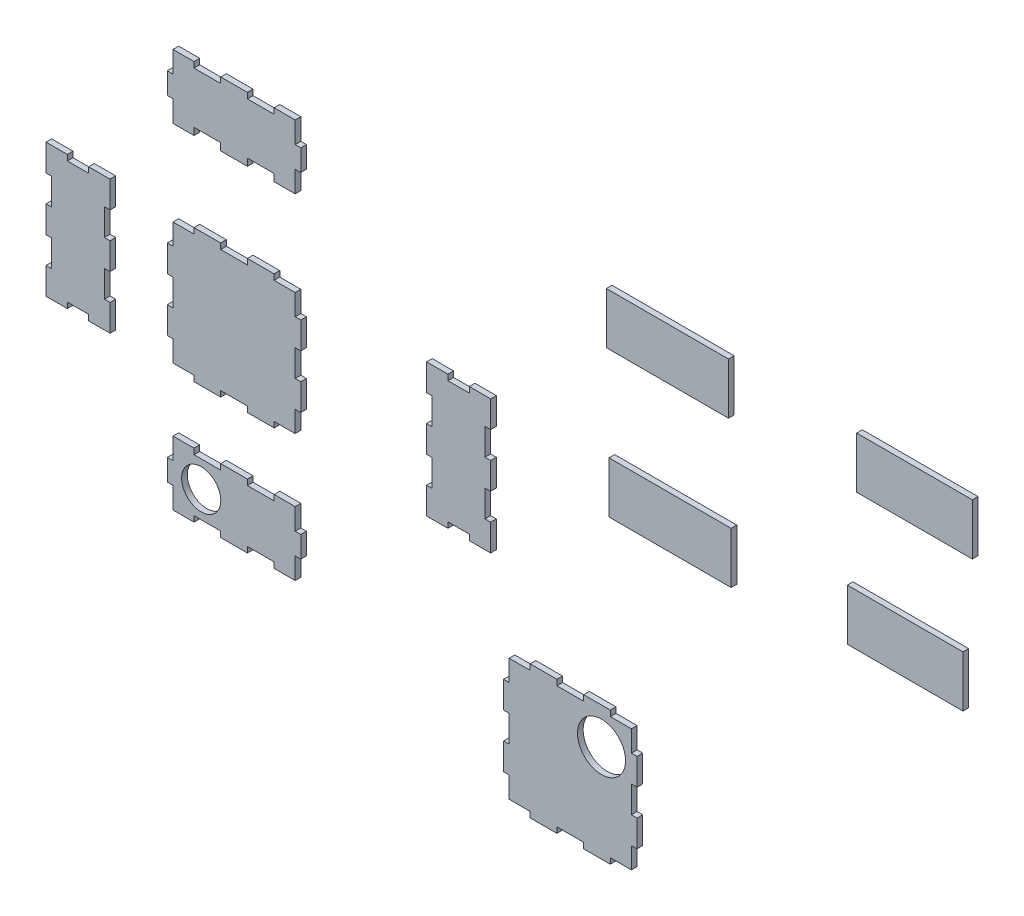
SolidWorks part; units mm, degrees
ref_plane "Front Plane" through (0, 0, 0) normal (0, 0, 1) x (1, 0, 0)
ref_plane "Top Plane" through (0, 0, 0) normal (0, 1, 0) x (1, 0, 0)
ref_plane "Right Plane" through (0, 0, 0) normal (1, 0, 0) x (0, 0, -1)
sketch "Sketch1" plane through (0, 0, 0) normal (0, 0, 1) x (1, 0, 0)
  line L0 (58.1679, -14.5353) -> (133.1679, -14.5353)
  line L1 (-130.7492, 103.2806) -> (-55.7492, 103.2806)
  line L2 (-130.7492, 103.2806) -> (-130.7492, 28.2806)
  line L3 (-130.7492, 28.2806) -> (-55.7492, 28.2806)
  line L4 (-55.7492, 103.2806) -> (-55.7492, 28.2806)
  line L5 (-130.7492, 184.0678) -> (-55.7492, 184.0678)
  line L6 (-130.7492, 184.0678) -> (-130.7492, 148.0678)
  line L7 (-130.7492, 148.0678) -> (-55.7492, 148.0678)
  line L8 (-55.7492, 184.0678) -> (-55.7492, 148.0678)
  line L9 (-162.8947, 103.2806) -> (-198.8947, 103.2806)
  line L10 (-162.8947, 103.2806) -> (-162.8947, 28.2806)
  line L11 (-162.8947, 28.2806) -> (-198.8947, 28.2806)
  line L12 (-198.8947, 103.2806) -> (-198.8947, 28.2806)
  line L13 (-130.7492, -4.048) -> (-55.7492, -4.048)
  line L14 (-130.7492, -4.048) -> (-130.7492, -40.048)
  line L15 (-130.7492, -40.048) -> (-55.7492, -40.048)
  line L16 (-55.7492, -4.048) -> (-55.7492, -40.048)
  line L17 (14.9083, 103.2806) -> (50.9083, 103.2806)
  line L18 (14.9083, 103.2806) -> (14.9083, 28.2806)
  line L19 (14.9083, 28.2806) -> (50.9083, 28.2806)
  line L20 (50.9083, 103.2806) -> (50.9083, 28.2806)
  line L21 (58.1679, -14.5353) -> (58.1679, -89.5353)
  line L22 (58.1679, -89.5353) -> (133.1679, -89.5353)
  line L23 (133.1679, -14.5353) -> (133.1679, -89.5353)
  line L24 (117.4177, 107.8353) -> (186.0177, 107.8353)
  line L25 (115.9298, 189.4652) -> (184.5298, 189.4652)
  line L26 (115.9298, 189.4652) -> (115.9298, 160.6652)
  line L27 (115.9298, 160.6652) -> (184.5298, 160.6652)
  line L28 (184.5298, 189.4652) -> (184.5298, 160.6652)
  line L29 (117.4177, 107.8353) -> (117.4177, 79.0353)
  line L30 (117.4177, 79.0353) -> (186.0177, 79.0353)
  line L31 (186.0177, 107.8353) -> (186.0177, 79.0353)
  line L32 (251.2924, 112.8623) -> (316.2924, 112.8623)
  line L33 (256.5253, 189.4652) -> (321.5253, 189.4652)
  line L34 (256.5253, 189.4652) -> (256.5253, 160.6652)
  line L35 (256.5253, 160.6652) -> (321.5253, 160.6652)
  line L36 (321.5253, 189.4652) -> (321.5253, 160.6652)
  line L37 (251.2924, 112.8623) -> (251.2924, 84.0623)
  line L38 (251.2924, 84.0623) -> (316.2924, 84.0623)
  line L39 (316.2924, 112.8623) -> (316.2924, 84.0623)
  dimension "D1" = 75
  dimension "D2" = 75
  dimension "D3" = 36
  dimension "D4" = 36
  dimension "D5" = 36
  dimension "D6" = 36
  dimension "D7" = 75
  dimension "D8" = 75
  dimension "D9" = 75
  dimension "D10" = 75
  dimension "D11" = 75
  dimension "D12" = 68.6
  dimension "D13" = 28.8
  dimension "D14" = 68.6
  dimension "D15" = 28.8
  dimension "D16" = 65
  dimension "D17" = 28.8
  dimension "D18" = 65
  dimension "D19" = 28.8
extrude "Boss-Extrude1" add sketch "Sketch1" along normal blind 3.18
sketch "Sketch2" plane through (0, 0, 3.18) normal (0, 0, 1) x (1, 0, 0)
  line L0 (-130.7492, 103.2806) -> (-130.7492, 28.2806) construction
  line L1 (-130.7492, 103.2806) -> (-127.5692, 103.2806)
  line L2 (-130.7492, 103.2806) -> (-130.7492, 88.2806)
  line L3 (-130.7492, 88.2806) -> (-127.5692, 88.2806)
  line L4 (-127.5692, 103.2806) -> (-127.5692, 88.2806)
  line L5 (-127.5692, 88.2806) -> (-130.7492, 88.2806)
  line L6 (-127.5692, 88.2806) -> (-127.5692, 73.2806)
  line L7 (-127.5692, 73.2806) -> (-130.7492, 73.2806)
  line L8 (-130.7492, 88.2806) -> (-130.7492, 73.2806)
  line L9 (-58.9292, 103.2806) -> (-55.7492, 103.2806)
  line L10 (-127.5692, 73.2806) -> (-130.7492, 73.2806)
  line L11 (-127.5692, 73.2806) -> (-127.5692, 58.2806)
  line L12 (-127.5692, 58.2806) -> (-130.7492, 58.2806)
  line L13 (-130.7492, 73.2806) -> (-130.7492, 58.2806)
  line L14 (-127.5692, 58.2806) -> (-130.7492, 58.2806)
  line L15 (-127.5692, 58.2806) -> (-127.5692, 43.2806)
  line L16 (-127.5692, 43.2806) -> (-130.7492, 43.2806)
  line L17 (-130.7492, 58.2806) -> (-130.7492, 43.2806)
  line L18 (-127.5692, 43.2806) -> (-130.7492, 43.2806)
  line L19 (58.1259, -14.5353) -> (61.3059, -14.5353)
  line L20 (-130.7492, 28.2806) -> (-115.7492, 28.2806)
  line L21 (-130.7492, 28.2806) -> (-130.7492, 31.4606)
  line L22 (-58.9292, 103.2806) -> (-58.9292, 88.2806)
  line L23 (-58.9292, 88.2806) -> (-55.7492, 88.2806)
  line L24 (-55.7492, 103.2806) -> (-55.7492, 88.2806)
  line L25 (-55.7492, 88.2806) -> (-58.9292, 88.2806)
  line L26 (-55.7492, 88.2806) -> (-55.7492, 73.2806)
  line L27 (-55.7492, 73.2806) -> (-58.9292, 73.2806)
  line L28 (-58.9292, 88.2806) -> (-58.9292, 73.2806)
  line L29 (-55.7492, 73.2806) -> (-58.9292, 73.2806)
  line L30 (-55.7492, 73.2806) -> (-55.7492, 58.2806)
  line L31 (-55.7492, 58.2806) -> (-58.9292, 58.2806)
  line L32 (-58.9292, 73.2806) -> (-58.9292, 58.2806)
  line L33 (-55.7492, 58.2806) -> (-58.9292, 58.2806)
  line L34 (-55.7492, 58.2806) -> (-55.7492, 43.2806)
  line L35 (-55.7492, 43.2806) -> (-58.9292, 43.2806)
  line L36 (-58.9292, 58.2806) -> (-58.9292, 43.2806)
  line L37 (-55.7492, 43.2806) -> (-58.9292, 43.2806)
  line L38 (-55.7492, 43.2806) -> (-55.7492, 28.2806)
  line L39 (-55.7492, 28.2806) -> (-58.9292, 28.2806)
  line L40 (-58.9292, 43.2806) -> (-58.9292, 28.2806)
  line L41 (-55.7492, 103.2806) -> (-130.7492, 103.2806) construction
  line L42 (-55.7492, 28.2806) -> (-55.7492, 103.2806) construction
  line L43 (-130.7492, 28.2806) -> (-55.7492, 28.2806) construction
  line L44 (-130.7492, 31.4606) -> (-115.7492, 31.4606)
  line L45 (-115.7492, 28.2806) -> (-115.7492, 31.4606)
  line L46 (-115.7492, 31.4606) -> (-100.7492, 31.4606)
  line L47 (-115.7492, 31.4606) -> (-115.7492, 28.2806)
  line L48 (-115.7492, 28.2806) -> (-100.7492, 28.2806)
  line L49 (-100.7492, 31.4606) -> (-100.7492, 28.2806)
  line L50 (-100.7492, 28.2806) -> (-85.7492, 28.2806)
  line L51 (-100.7492, 28.2806) -> (-100.7492, 31.4606)
  line L52 (-100.7492, 31.4606) -> (-85.7492, 31.4606)
  line L53 (-85.7492, 28.2806) -> (-85.7492, 31.4606)
  line L54 (-85.7492, 31.4606) -> (-70.7492, 31.4606)
  line L55 (-85.7492, 31.4606) -> (-85.7492, 28.2806)
  line L56 (-85.7492, 28.2806) -> (-70.7492, 28.2806)
  line L57 (-70.7492, 31.4606) -> (-70.7492, 28.2806)
  line L58 (-70.7492, 28.2806) -> (-55.7492, 28.2806)
  line L59 (-70.7492, 28.2806) -> (-70.7492, 31.4606)
  line L60 (-70.7492, 31.4606) -> (-55.7492, 31.4606)
  line L61 (-55.7492, 28.2806) -> (-55.7492, 31.4606)
  line L62 (-127.5692, 43.2806) -> (-130.7492, 43.2806)
  line L63 (-127.5692, 43.2806) -> (-127.5692, 28.2806)
  line L64 (-127.5692, 28.2806) -> (-130.7492, 28.2806)
  line L65 (-130.7492, 43.2806) -> (-130.7492, 28.2806)
  line L66 (-130.7492, 103.2806) -> (-115.7492, 103.2806)
  line L67 (-130.7492, 103.2806) -> (-130.7492, 100.1006)
  line L68 (-130.7492, 100.1006) -> (-115.7492, 100.1006)
  line L69 (-115.7492, 103.2806) -> (-115.7492, 100.1006)
  line L70 (-115.7492, 100.1006) -> (-100.7492, 100.1006)
  line L71 (-115.7492, 100.1006) -> (-115.7492, 103.2806)
  line L72 (-115.7492, 103.2806) -> (-100.7492, 103.2806)
  line L73 (-100.7492, 100.1006) -> (-100.7492, 103.2806)
  line L74 (-100.7492, 100.1006) -> (-85.7492, 100.1006)
  line L75 (-100.7492, 100.1006) -> (-100.7492, 103.2806)
  line L76 (-100.7492, 103.2806) -> (-85.7492, 103.2806)
  line L77 (-85.7492, 100.1006) -> (-85.7492, 103.2806)
  line L78 (-85.7492, 100.1006) -> (-70.7492, 100.1006)
  line L79 (-85.7492, 100.1006) -> (-85.7492, 103.2806)
  line L80 (-85.7492, 103.2806) -> (-70.7492, 103.2806)
  line L81 (-70.7492, 100.1006) -> (-70.7492, 103.2806)
  line L82 (-70.7492, 100.1006) -> (-55.7492, 100.1006)
  line L83 (-70.7492, 100.1006) -> (-70.7492, 103.2806)
  line L84 (-70.7492, 103.2806) -> (-55.7492, 103.2806)
  line L85 (-55.7492, 100.1006) -> (-55.7492, 103.2806)
  line L86 (58.1259, -14.5353) -> (58.1259, -29.5353)
  line L87 (58.1259, -29.5353) -> (61.3059, -29.5353)
  line L88 (61.3059, -14.5353) -> (61.3059, -29.5353)
  line L89 (61.3059, -29.5353) -> (58.1259, -29.5353)
  line L90 (61.3059, -29.5353) -> (61.3059, -44.5353)
  line L91 (61.3059, -44.5353) -> (58.1259, -44.5353)
  line L92 (58.1259, -29.5353) -> (58.1259, -44.5353)
  line L93 (129.9879, -14.5353) -> (133.1679, -14.5353)
  line L94 (61.3059, -44.5353) -> (58.1259, -44.5353)
  line L95 (61.3059, -44.5353) -> (61.3059, -59.5353)
  line L96 (61.3059, -59.5353) -> (58.1259, -59.5353)
  line L97 (58.1259, -44.5353) -> (58.1259, -59.5353)
  line L98 (61.3059, -59.5353) -> (58.1259, -59.5353)
  line L99 (61.3059, -59.5353) -> (61.3059, -74.5353)
  line L100 (61.3059, -74.5353) -> (58.1259, -74.5353)
  line L101 (58.1259, -59.5353) -> (58.1259, -74.5353)
  line L102 (61.3059, -74.5353) -> (58.1259, -74.5353)
  line L103 (58.1259, -89.5401) -> (73.1259, -89.5401)
  line L104 (58.1259, -89.5401) -> (58.1259, -86.3601)
  line L105 (129.9879, -14.5353) -> (129.9879, -29.5353)
  line L106 (129.9879, -29.5353) -> (133.1679, -29.5353)
  line L107 (133.1679, -14.5353) -> (133.1679, -29.5353)
  line L108 (133.1679, -29.5353) -> (129.9879, -29.5353)
  line L109 (133.1679, -29.5353) -> (133.1679, -44.5353)
  line L110 (133.1679, -44.5353) -> (129.9879, -44.5353)
  line L111 (129.9879, -29.5353) -> (129.9879, -44.5353)
  line L112 (133.1679, -44.5353) -> (129.9879, -44.5353)
  line L113 (133.1679, -44.5353) -> (133.1679, -59.5353)
  line L114 (133.1679, -59.5353) -> (129.9879, -59.5353)
  line L115 (129.9879, -44.5353) -> (129.9879, -59.5353)
  line L116 (133.1679, -59.5353) -> (129.9879, -59.5353)
  line L117 (133.1679, -59.5353) -> (133.1679, -74.5353)
  line L118 (133.1679, -74.5353) -> (129.9879, -74.5353)
  line L119 (129.9879, -59.5353) -> (129.9879, -74.5353)
  line L120 (133.1679, -74.5353) -> (129.9879, -74.5353)
  line L121 (133.1679, -74.5353) -> (133.1679, -89.5401)
  line L122 (133.1679, -89.5401) -> (129.9879, -89.5401)
  line L123 (129.9879, -74.5353) -> (129.9879, -89.5401)
  line L124 (58.1259, -86.3601) -> (73.1259, -86.3601)
  line L125 (73.1259, -89.5401) -> (73.1259, -86.3601)
  line L126 (73.1259, -86.3601) -> (88.1259, -86.3601)
  line L127 (73.1259, -86.3601) -> (73.1259, -89.5401)
  line L128 (73.1259, -89.5401) -> (88.1259, -89.5401)
  line L129 (88.1259, -86.3601) -> (88.1259, -89.5401)
  line L130 (88.1259, -89.5401) -> (103.1259, -89.5401)
  line L131 (88.1259, -89.5401) -> (88.1259, -86.3601)
  line L132 (88.1259, -86.3601) -> (103.1259, -86.3601)
  line L133 (103.1259, -89.5401) -> (103.1259, -86.3601)
  line L134 (103.1259, -86.3601) -> (118.1259, -86.3601)
  line L135 (103.1259, -86.3601) -> (103.1259, -89.5401)
  line L136 (103.1259, -89.5401) -> (118.1259, -89.5401)
  line L137 (118.1259, -86.3601) -> (118.1259, -89.5401)
  line L138 (118.1259, -89.5401) -> (133.1679, -89.5401)
  line L139 (118.1259, -89.5401) -> (118.1259, -86.3601)
  line L140 (118.1259, -86.3601) -> (133.1679, -86.3601)
  line L141 (133.1679, -89.5401) -> (133.1679, -86.3601)
  line L142 (61.3059, -74.5353) -> (58.1259, -74.5353)
  line L143 (61.3059, -74.5353) -> (61.3059, -89.5401)
  line L144 (61.3059, -89.5401) -> (58.1259, -89.5401)
  line L145 (58.1259, -74.5353) -> (58.1259, -89.5401)
  line L146 (58.1259, -14.5353) -> (73.1259, -14.5353)
  line L147 (58.1259, -14.5353) -> (58.1259, -17.7153)
  line L148 (58.1259, -17.7153) -> (73.1259, -17.7153)
  line L149 (73.1259, -14.5353) -> (73.1259, -17.7153)
  line L150 (73.1259, -17.7153) -> (88.1259, -17.7153)
  line L151 (73.1259, -17.7153) -> (73.1259, -14.5353)
  line L152 (73.1259, -14.5353) -> (88.1259, -14.5353)
  line L153 (88.1259, -17.7153) -> (88.1259, -14.5353)
  line L154 (88.1259, -17.7153) -> (103.1259, -17.7153)
  line L155 (88.1259, -17.7153) -> (88.1259, -14.5353)
  line L156 (88.1259, -14.5353) -> (103.1259, -14.5353)
  line L157 (103.1259, -17.7153) -> (103.1259, -14.5353)
  line L158 (103.1259, -17.7153) -> (118.1259, -17.7153)
  line L159 (103.1259, -17.7153) -> (103.1259, -14.5353)
  line L160 (103.1259, -14.5353) -> (118.1259, -14.5353)
  line L161 (118.1259, -17.7153) -> (118.1259, -14.5353)
  line L162 (118.1259, -17.7153) -> (133.1679, -17.7153)
  line L163 (118.1259, -17.7153) -> (118.1259, -14.5353)
  line L164 (118.1259, -14.5353) -> (133.1679, -14.5353)
  line L165 (133.1679, -17.7153) -> (133.1679, -14.5353)
  line L166 (133.1679, -14.5353) -> (58.1679, -14.5353) construction
  line L167 (133.1679, -89.5353) -> (133.1679, -14.5353) construction
  point P99 (58.1781, -14.5353)
  point P102 (133.1679, -14.5353)
  point P104 (133.1679, -14.5353)
  line M6 (-130.7492, 103.2806) -> (-130.7492, 28.2806)
  line M7 (-130.7492, 28.2806) -> (-55.7492, 28.2806)
  line M8 (-55.7492, 28.2806) -> (-55.7492, 103.2806)
  line M9 (-55.7492, 103.2806) -> (-130.7492, 103.2806)
  dimension "D1" = 15
  dimension "D2" = 15
  dimension "D3" = 15
  dimension "D4" = 15
  dimension "D5" = 15
  dimension "D6" = 15
  dimension "D7" = 15
  dimension "D8" = 15
  dimension "D9" = 3.18
  dimension "D10" = 15
  dimension "D11" = 15
  dimension "D12" = 15
  dimension "D13" = 15
  dimension "D14" = 15
  dimension "D15" = 15
  dimension "D16" = 15
  dimension "D17" = 15
  dimension "D18" = 3.18
  dimension "D19" = 3.18
  dimension "D20" = 3.18
  dimension "D21" = 15
  dimension "D22" = 15
  dimension "D23" = 15
  dimension "D24" = 15
  dimension "D25" = 15
  dimension "D26" = 15
  dimension "D27" = 15
  dimension "D28" = 15
  dimension "D29" = 3.18
  dimension "D30" = 15
  dimension "D31" = 15
  dimension "D32" = 15
  dimension "D33" = 15
  dimension "D34" = 15
  dimension "D35" = 15
  dimension "D36" = 15
  dimension "D37" = 15
  dimension "D38" = 3.18
  dimension "D39" = 3.18
  dimension "D40" = 3.18
extrude "Cut-Extrude1" cut sketch "Sketch2" against normal blind 3.18 contours L12 L11 L7 M6 region at (-129.1592, 65.7806, 3.18)
extrude "Cut-Extrude2" cut sketch "Sketch2<4>" against normal blind 3.18 contours L68 L2 L3 L4 | L68 L4 M6 M9 | L69 L4 L68 M9 | L74 L77 L73 M9 | L81 L82 L22 M9 | L22 L82 L24 M9 | L82 L22 L23 M8 | L27 L32 L31 M8 | L40 L60 L38 L35 | L60 L40 M7 M8 | L60 L57 L40 M7 | L53 L52 L49 M7 | L44 L63 L20 L45 | L63 L44 M6 M7 | L63 L16 L44 M6 region at (-129.1592, 101.6906, 3.18) region at (-121.6592, 101.6906, 3.18) region at (-129.1592, 94.1906, 3.18) region at (-93.2492, 101.6906, 3.18) region at (-64.8392, 101.6906, 3.18) region at (-129.1592, 37.3706, 3.18) region at (-57.3392, 101.6906, 3.18) region at (-129.1592, 29.8706, 3.18) region at (-121.6592, 29.8706, 3.18) region at (-57.3392, 94.1906, 3.18) region at (-93.2492, 29.8706, 3.18) region at (-57.3392, 65.7806, 3.18) region at (-64.8392, 29.8706, 3.18) region at (-57.3392, 37.3706, 3.18) region at (-57.3392, 29.8706, 3.18)
sketch "Sketch2<4>" plane through (0, 0, 3.18) normal (0, 0, 1) x (1, 0, 0) same geometry as "Sketch2"
sketch "Sketch3" plane through (0, 0, 3.18) normal (0, 0, 1) x (1, 0, 0)
  line L0 (-162.8947, 28.2806) -> (-162.8947, 103.2806) construction
  line L1 (-162.8947, 103.2806) -> (-166.0747, 103.2806)
  line L2 (-162.8947, 103.2806) -> (-162.8947, 88.2806)
  line L3 (-162.8947, 88.2806) -> (-166.0747, 88.2806)
  line L4 (-166.0747, 103.2806) -> (-166.0747, 88.2806)
  line L5 (-166.0747, 88.2806) -> (-162.8947, 88.2806)
  line L6 (-166.0747, 88.2806) -> (-166.0747, 73.2806)
  line L7 (-166.0747, 73.2806) -> (-162.8947, 73.2806)
  line L8 (-162.8947, 88.2806) -> (-162.8947, 73.2806)
  line L9 (-198.8947, 28.2806) -> (-162.8947, 28.2806) construction
  line L10 (-162.8947, 73.2806) -> (-166.0747, 73.2806)
  line L11 (-162.8947, 73.2806) -> (-162.8947, 58.2806)
  line L12 (-162.8947, 58.2806) -> (-166.0747, 58.2806)
  line L13 (-166.0747, 73.2806) -> (-166.0747, 58.2806)
  line L14 (-166.0747, 58.2806) -> (-162.8947, 58.2806)
  line L15 (-166.0747, 58.2806) -> (-166.0747, 43.2806)
  line L16 (-166.0747, 43.2806) -> (-162.8947, 43.2806)
  line L17 (-162.8947, 58.2806) -> (-162.8947, 43.2806)
  line L18 (-162.8947, 43.2806) -> (-166.0747, 43.2806)
  line L19 (-162.8947, 43.2806) -> (-162.8947, 28.2806)
  line L20 (-162.8947, 28.2806) -> (-166.0747, 28.2806)
  line L21 (-166.0747, 43.2806) -> (-166.0747, 28.2806)
  line L22 (14.9083, 103.2806) -> (18.0783, 103.2806)
  line L23 (14.9083, 103.2806) -> (14.9083, 88.2806)
  line L24 (14.9083, 88.2806) -> (18.0783, 88.2806)
  line L25 (18.0783, 103.2806) -> (18.0783, 88.2806)
  line L26 (18.0783, 88.2806) -> (14.9083, 88.2806)
  line L27 (18.0783, 88.2806) -> (18.0783, 73.2806)
  line L28 (18.0783, 73.2806) -> (14.9083, 73.2806)
  line L29 (14.9083, 88.2806) -> (14.9083, 73.2806)
  line L30 (14.9083, 73.2806) -> (18.0783, 73.2806)
  line L31 (14.9083, 73.2806) -> (14.9083, 58.2806)
  line L32 (14.9083, 58.2806) -> (18.0783, 58.2806)
  line L33 (18.0783, 73.2806) -> (18.0783, 58.2806)
  line L34 (18.0783, 58.2806) -> (14.9083, 58.2806)
  line L35 (18.0783, 58.2806) -> (18.0783, 43.2806)
  line L36 (18.0783, 43.2806) -> (14.9083, 43.2806)
  line L37 (14.9083, 58.2806) -> (14.9083, 43.2806)
  line L38 (14.9083, 28.2806) -> (50.9083, 28.2806) construction
  line L39 (18.0783, 43.2806) -> (14.9083, 43.2806)
  line L40 (18.0783, 43.2806) -> (18.0783, 28.2806)
  line L41 (18.0783, 28.2806) -> (14.9083, 28.2806)
  line L42 (14.9083, 43.2806) -> (14.9083, 28.2806)
  line L43 (14.9083, 103.2806) -> (14.9083, 28.2806) construction
  line L44 (-130.7492, 148.0678) -> (-55.7492, 148.0678) construction
  line L45 (-130.7492, 148.0678) -> (-115.7492, 148.0678)
  line L46 (-130.7492, 148.0678) -> (-130.7492, 152.096)
  line L47 (-130.7492, 152.096) -> (-115.7492, 152.096)
  line L48 (-115.7492, 148.0678) -> (-115.7492, 152.096)
  line L49 (-115.7492, 152.096) -> (-100.7492, 152.096)
  line L50 (-115.7492, 152.096) -> (-115.7492, 148.0678)
  line L51 (-115.7492, 148.0678) -> (-100.7492, 148.0678)
  line L52 (-100.7492, 152.096) -> (-100.7492, 148.0678)
  line L53 (-55.7492, 148.0678) -> (-55.7492, 184.0678) construction
  line L54 (-100.7492, 148.0678) -> (-85.7492, 148.0678)
  line L55 (-100.7492, 148.0678) -> (-100.7492, 152.096)
  line L56 (-100.7492, 152.096) -> (-85.7492, 152.096)
  line L57 (-85.7492, 148.0678) -> (-85.7492, 152.096)
  line L58 (-85.7492, 152.096) -> (-70.7492, 152.096)
  line L59 (-85.7492, 152.096) -> (-85.7492, 148.0678)
  line L60 (-85.7492, 148.0678) -> (-70.7492, 148.0678)
  line L61 (-70.7492, 152.096) -> (-70.7492, 148.0678)
  line L62 (-70.7492, 148.0678) -> (-55.7492, 148.0678)
  line L63 (-70.7492, 148.0678) -> (-70.7492, 152.096)
  line L64 (-70.7492, 152.096) -> (-55.7492, 152.096)
  line L65 (-55.7492, 148.0678) -> (-55.7492, 152.096)
  line L66 (-130.7492, -7.228) -> (-115.7492, -7.228)
  line L67 (-130.7492, -7.228) -> (-130.7492, -4.048)
  line L68 (-130.7492, -4.048) -> (-115.7492, -4.048)
  line L69 (-115.7492, -7.228) -> (-115.7492, -4.048)
  line L70 (-115.7492, -4.048) -> (-100.7492, -4.048)
  line L71 (-115.7492, -4.048) -> (-115.7492, -7.228)
  line L72 (-115.7492, -7.228) -> (-100.7492, -7.228)
  line L73 (-100.7492, -4.048) -> (-100.7492, -7.228)
  line L74 (-100.7492, -7.228) -> (-85.7492, -7.228)
  line L75 (-100.7492, -7.228) -> (-100.7492, -4.048)
  line L76 (-100.7492, -4.048) -> (-85.7492, -4.048)
  line L77 (-85.7492, -7.228) -> (-85.7492, -4.048)
  line L78 (-85.7492, -4.048) -> (-70.7492, -4.048)
  line L79 (-85.7492, -4.048) -> (-85.7492, -7.228)
  line L80 (-85.7492, -7.228) -> (-70.7492, -7.228)
  line L81 (-70.7492, -4.048) -> (-70.7492, -7.228)
  line L82 (-70.7492, -7.228) -> (-55.7492, -7.228)
  line L83 (-70.7492, -7.228) -> (-70.7492, -4.048)
  line L84 (-70.7492, -4.048) -> (-55.7492, -4.048)
  line L85 (-55.7492, -7.228) -> (-55.7492, -4.048)
  line L86 (-55.7492, -4.048) -> (-130.7492, -4.048) construction
  line L87 (50.9083, 103.2806) -> (14.9083, 103.2806) construction
  line L88 (-198.8947, 103.2806) -> (-186.8947, 103.2806)
  line L89 (-198.8947, 103.2806) -> (-198.8947, 100.1006)
  line L90 (-198.8947, 100.1006) -> (-186.8947, 100.1006)
  line L91 (-186.8947, 103.2806) -> (-186.8947, 100.1006)
  line L92 (-186.8947, 103.2806) -> (-174.8947, 103.2806)
  line L93 (-186.8947, 103.2806) -> (-186.8947, 100.1006)
  line L94 (-186.8947, 100.1006) -> (-174.8947, 100.1006)
  line L95 (-174.8947, 103.2806) -> (-174.8947, 100.1006)
  line L96 (-174.8947, 100.1006) -> (-162.8947, 100.1006)
  line L97 (-174.8947, 100.1006) -> (-174.8947, 103.2806)
  line L98 (-174.8947, 103.2806) -> (-162.8947, 103.2806)
  line L99 (-162.8947, 100.1006) -> (-162.8947, 103.2806)
  line L100 (-198.8947, 28.2806) -> (-186.8947, 28.2806)
  line L101 (-198.8947, 28.2806) -> (-198.8947, 31.4606)
  line L102 (-198.8947, 31.4606) -> (-186.8947, 31.4606)
  line L103 (-186.8947, 28.2806) -> (-186.8947, 31.4606)
  line L104 (-186.8947, 31.4606) -> (-174.8947, 31.4606)
  line L105 (-186.8947, 31.4606) -> (-186.8947, 28.2806)
  line L106 (-186.8947, 28.2806) -> (-174.8947, 28.2806)
  line L107 (-174.8947, 31.4606) -> (-174.8947, 28.2806)
  line L108 (-174.8947, 31.4606) -> (-162.8947, 31.4606)
  line L109 (-174.8947, 31.4606) -> (-174.8947, 28.2806)
  line L110 (-174.8947, 28.2806) -> (-162.8947, 28.2806)
  line L111 (-162.8947, 31.4606) -> (-162.8947, 28.2806)
  line L112 (14.9083, 103.2806) -> (26.9083, 103.2806)
  line L113 (14.9083, 103.2806) -> (14.9083, 100.1006)
  line L114 (14.9083, 100.1006) -> (26.9083, 100.1006)
  line L115 (26.9083, 103.2806) -> (26.9083, 100.1006)
  line L116 (26.9083, 100.1006) -> (38.9083, 100.1006)
  line L117 (26.9083, 100.1006) -> (26.9083, 103.2806)
  line L118 (26.9083, 103.2806) -> (38.9083, 103.2806)
  line L119 (38.9083, 100.1006) -> (38.9083, 103.2806)
  line L120 (50.9083, 28.2806) -> (50.9083, 103.2806) construction
  line L121 (38.9083, 103.2806) -> (50.9083, 103.2806)
  line L122 (38.9083, 103.2806) -> (38.9083, 100.1006)
  line L123 (38.9083, 100.1006) -> (50.9083, 100.1006)
  line L124 (50.9083, 103.2806) -> (50.9083, 100.1006)
  line L125 (-130.7492, -4.048) -> (-130.7492, -40.048) construction
  line L126 (14.9083, 28.2806) -> (26.9083, 28.2806)
  line L127 (14.9083, 28.2806) -> (14.9083, 31.4606)
  line L128 (14.9083, 31.4606) -> (26.9083, 31.4606)
  line L129 (26.9083, 28.2806) -> (26.9083, 31.4606)
  line L130 (26.9083, 31.4606) -> (38.9083, 31.4606)
  line L131 (26.9083, 31.4606) -> (26.9083, 28.2806)
  line L132 (26.9083, 28.2806) -> (38.9083, 28.2806)
  line L133 (38.9083, 31.4606) -> (38.9083, 28.2806)
  line L134 (38.9083, 31.4606) -> (50.9083, 31.4606)
  line L135 (38.9083, 31.4606) -> (38.9083, 28.2806)
  line L136 (38.9083, 28.2806) -> (50.9083, 28.2806)
  line L137 (50.9083, 31.4606) -> (50.9083, 28.2806)
  line L138 (-130.7492, -4.048) -> (-127.5692, -4.048)
  line L139 (-130.7492, -4.048) -> (-130.7492, -16.048)
  line L140 (-130.7492, -16.048) -> (-127.5692, -16.048)
  line L141 (-127.5692, -4.048) -> (-127.5692, -16.048)
  line L142 (-127.5692, -16.048) -> (-130.7492, -16.048)
  line L143 (-127.5692, -16.048) -> (-127.5692, -28.048)
  line L144 (-127.5692, -28.048) -> (-130.7492, -28.048)
  line L145 (-130.7492, -16.048) -> (-130.7492, -28.048)
  line L146 (-198.8947, 103.2806) -> (-198.8947, 28.2806) construction
  line L147 (-127.5692, -28.048) -> (-130.7492, -28.048)
  line L148 (-127.5692, -28.048) -> (-127.5692, -40.048)
  line L149 (-127.5692, -40.048) -> (-130.7492, -40.048)
  line L150 (-130.7492, -28.048) -> (-130.7492, -40.048)
  line L151 (-55.7492, -4.048) -> (-58.9292, -4.048)
  line L152 (-55.7492, -4.048) -> (-55.7492, -16.048)
  line L153 (-55.7492, -16.048) -> (-58.9292, -16.048)
  line L154 (-58.9292, -4.048) -> (-58.9292, -16.048)
  line L155 (-58.9292, -16.048) -> (-55.7492, -16.048)
  line L156 (-58.9292, -16.048) -> (-58.9292, -28.048)
  line L157 (-58.9292, -28.048) -> (-55.7492, -28.048)
  line L158 (-55.7492, -16.048) -> (-55.7492, -28.048)
  line L159 (-198.8947, 103.2806) -> (-195.7147, 103.2806)
  line L160 (-198.8947, 103.2806) -> (-198.8947, 88.2806)
  line L161 (-58.9292, -28.048) -> (-55.7492, -28.048)
  line L162 (-58.9292, -28.048) -> (-58.9292, -40.048)
  line L163 (-58.9292, -40.048) -> (-55.7492, -40.048)
  line L164 (-55.7492, -28.048) -> (-55.7492, -40.048)
  line L165 (-198.8947, 88.2806) -> (-195.7147, 88.2806)
  line L166 (-130.7492, 184.0678) -> (-130.7492, 148.0678) construction
  line L167 (-130.7492, 184.0678) -> (-127.5692, 184.0678)
  line L168 (-130.7492, 184.0678) -> (-130.7492, 172.0678)
  line L169 (-130.7492, 172.0678) -> (-127.5692, 172.0678)
  line L170 (-127.5692, 184.0678) -> (-127.5692, 172.0678)
  line L171 (-127.5692, 172.0678) -> (-130.7492, 172.0678)
  line L172 (-127.5692, 172.0678) -> (-127.5692, 160.0678)
  line L173 (-127.5692, 160.0678) -> (-130.7492, 160.0678)
  line L174 (-130.7492, 172.0678) -> (-130.7492, 160.0678)
  line L175 (-195.7147, 103.2806) -> (-195.7147, 88.2806)
  line L176 (-127.5692, 160.0678) -> (-130.7492, 160.0678)
  line L177 (-127.5692, 160.0678) -> (-127.5692, 148.0678)
  line L178 (-127.5692, 148.0678) -> (-130.7492, 148.0678)
  line L179 (-130.7492, 160.0678) -> (-130.7492, 148.0678)
  line L180 (-55.7492, 184.0678) -> (-58.9292, 184.0678)
  line L181 (-55.7492, 184.0678) -> (-55.7492, 172.0678)
  line L182 (-55.7492, 172.0678) -> (-58.9292, 172.0678)
  line L183 (-58.9292, 184.0678) -> (-58.9292, 172.0678)
  line L184 (-58.9292, 172.0678) -> (-55.7492, 172.0678)
  line L185 (-58.9292, 172.0678) -> (-58.9292, 160.0678)
  line L186 (-58.9292, 160.0678) -> (-55.7492, 160.0678)
  line L187 (-55.7492, 172.0678) -> (-55.7492, 160.0678)
  line L188 (-58.9292, 160.0678) -> (-55.7492, 160.0678)
  line L189 (-58.9292, 160.0678) -> (-58.9292, 148.0678)
  line L190 (-58.9292, 148.0678) -> (-55.7492, 148.0678)
  line L191 (-55.7492, 160.0678) -> (-55.7492, 148.0678)
  line L192 (-195.7147, 88.2806) -> (-198.8947, 88.2806)
  line L193 (-195.7147, 88.2806) -> (-195.7147, 73.2806)
  line L194 (-195.7147, 73.2806) -> (-198.8947, 73.2806)
  line L195 (-198.8947, 88.2806) -> (-198.8947, 73.2806)
  line L196 (-55.7492, 184.0678) -> (-130.7492, 184.0678) construction
  line L197 (-195.7147, 73.2806) -> (-198.8947, 73.2806)
  line L198 (-195.7147, 73.2806) -> (-195.7147, 58.2806)
  line L199 (-195.7147, 58.2806) -> (-198.8947, 58.2806)
  line L200 (-198.8947, 73.2806) -> (-198.8947, 58.2806)
  line L201 (-195.7147, 58.2806) -> (-198.8947, 58.2806)
  line L202 (-195.7147, 58.2806) -> (-195.7147, 43.2806)
  line L203 (-195.7147, 43.2806) -> (-198.8947, 43.2806)
  line L204 (-198.8947, 58.2806) -> (-198.8947, 43.2806)
  line L205 (-195.7147, 43.2806) -> (-198.8947, 43.2806)
  line L206 (-195.7147, 43.2806) -> (-195.7147, 28.2806)
  line L207 (-195.7147, 28.2806) -> (-198.8947, 28.2806)
  line L208 (-198.8947, 43.2806) -> (-198.8947, 28.2806)
  line L209 (50.9083, 103.2806) -> (47.7283, 103.2806)
  line L210 (50.9083, 103.2806) -> (50.9083, 88.2806)
  line L211 (50.9083, 88.2806) -> (47.7283, 88.2806)
  line L212 (47.7283, 103.2806) -> (47.7283, 88.2806)
  line L213 (47.7283, 88.2806) -> (50.9083, 88.2806)
  line L214 (47.7283, 88.2806) -> (47.7283, 73.2806)
  line L215 (47.7283, 73.2806) -> (50.9083, 73.2806)
  line L216 (50.9083, 88.2806) -> (50.9083, 73.2806)
  line L217 (50.9083, 73.2806) -> (47.7283, 73.2806)
  line L218 (50.9083, 73.2806) -> (50.9083, 58.2806)
  line L219 (50.9083, 58.2806) -> (47.7283, 58.2806)
  line L220 (47.7283, 73.2806) -> (47.7283, 58.2806)
  line L221 (47.7283, 58.2806) -> (50.9083, 58.2806)
  line L222 (47.7283, 58.2806) -> (47.7283, 43.2806)
  line L223 (47.7283, 43.2806) -> (50.9083, 43.2806)
  line L224 (50.9083, 58.2806) -> (50.9083, 43.2806)
  line L225 (47.7283, 43.2806) -> (50.9083, 43.2806)
  line L226 (47.7283, 43.2806) -> (47.7283, 28.2806)
  line L227 (47.7283, 28.2806) -> (50.9083, 28.2806)
  line L228 (50.9083, 43.2806) -> (50.9083, 28.2806)
  line L229 (-130.7492, 184.0678) -> (-115.7492, 184.0678)
  line L230 (-130.7492, 184.0678) -> (-130.7492, 180.8878)
  line L231 (-130.7492, 180.8878) -> (-115.7492, 180.8878)
  line L232 (-115.7492, 184.0678) -> (-115.7492, 180.8878)
  line L233 (-115.7492, 180.8878) -> (-100.7492, 180.8878)
  line L234 (-115.7492, 180.8878) -> (-115.7492, 184.0678)
  line L235 (-115.7492, 184.0678) -> (-100.7492, 184.0678)
  line L236 (-100.7492, 180.8878) -> (-100.7492, 184.0678)
  line L237 (-130.7492, -40.048) -> (-55.7492, -40.048) construction
  line L238 (-100.7492, 184.0678) -> (-85.7492, 184.0678)
  line L239 (-100.7492, 184.0678) -> (-100.7492, 180.8878)
  line L240 (-100.7492, 180.8878) -> (-85.7492, 180.8878)
  line L241 (-85.7492, 184.0678) -> (-85.7492, 180.8878)
  line L242 (-85.7492, 180.8878) -> (-70.7492, 180.8878)
  line L243 (-85.7492, 180.8878) -> (-85.7492, 184.0678)
  line L244 (-85.7492, 184.0678) -> (-70.7492, 184.0678)
  line L245 (-70.7492, 180.8878) -> (-70.7492, 184.0678)
  line L246 (-70.7492, 180.8878) -> (-55.7492, 180.8878)
  line L247 (-70.7492, 180.8878) -> (-70.7492, 184.0678)
  line L248 (-70.7492, 184.0678) -> (-55.7492, 184.0678)
  line L249 (-55.7492, 180.8878) -> (-55.7492, 184.0678)
  line L250 (-130.7492, -40.048) -> (-115.7492, -40.048)
  line L251 (-130.7492, -40.048) -> (-130.7492, -36.868)
  line L252 (-130.7492, -36.868) -> (-115.7492, -36.868)
  line L253 (-115.7492, -40.048) -> (-115.7492, -36.868)
  line L254 (-115.7492, -36.868) -> (-100.7492, -36.868)
  line L255 (-115.7492, -36.868) -> (-115.7492, -40.048)
  line L256 (-115.7492, -40.048) -> (-100.7492, -40.048)
  line L257 (-100.7492, -36.868) -> (-100.7492, -40.048)
  line L259 (-100.7492, -40.048) -> (-85.7492, -40.048)
  line L260 (-100.7492, -40.048) -> (-100.7492, -36.868)
  line L261 (-100.7492, -36.868) -> (-85.7492, -36.868)
  line L262 (-85.7492, -40.048) -> (-85.7492, -36.868)
  line L263 (-85.7492, -36.868) -> (-70.7492, -36.868)
  line L264 (-85.7492, -36.868) -> (-85.7492, -40.048)
  line L265 (-85.7492, -40.048) -> (-70.7492, -40.048)
  line L266 (-70.7492, -36.868) -> (-70.7492, -40.048)
  line L267 (-70.7492, -40.048) -> (-55.7492, -40.048)
  line L268 (-70.7492, -40.048) -> (-70.7492, -36.868)
  line L269 (-70.7492, -36.868) -> (-55.7492, -36.868)
  line L270 (-55.7492, -40.048) -> (-55.7492, -36.868)
  line M35 (-162.8947, 28.2806) -> (-162.8947, 103.2806)
  line M36 (-162.8947, 103.2806) -> (-198.8947, 103.2806)
  line M37 (-198.8947, 103.2806) -> (-198.8947, 28.2806)
  line M38 (-198.8947, 28.2806) -> (-162.8947, 28.2806)
  dimension "D1" = 3.18
  dimension "D2" = 15
  dimension "D3" = 15
  dimension "D4" = 15
  dimension "D5" = 15
  dimension "D6" = 3.17
  dimension "D7" = 15
  dimension "D8" = 15
  dimension "D9" = 15
  dimension "D10" = 15
  dimension "D11" = 15
  dimension "D12" = 15
  dimension "D13" = 15
  dimension "D14" = 15
  dimension "D15" = 15
  dimension "D16" = 15
  dimension "D17" = 15
  dimension "D18" = 15
  dimension "D19" = 15
  dimension "D20" = 3.18
  dimension "D21" = 12
  dimension "D22" = 12
  dimension "D23" = 3.18
  dimension "D24" = 3.18
  dimension "D25" = 12
  dimension "D26" = 12
  dimension "D27" = 3.18
  dimension "D28" = 3.18
  dimension "D29" = 12
  dimension "D30" = 12
  dimension "D31" = 3.18
  dimension "D32" = 3.18
  dimension "D33" = 12
  dimension "D34" = 3.18
  dimension "D35" = 12
  dimension "D36" = 12
  dimension "D37" = 3.18
  dimension "D38" = 15
  dimension "D39" = 3.18
  dimension "D40" = 15
  dimension "D41" = 3.18
  dimension "D42" = 3.18
extrude "Cut-Extrude3" cut sketch "Sketch3" against normal blind 3.18 contours L52 L49 L48 L51 | L61 L58 L57 L60 region at (-108.2492, 150.0819, 3.18) region at (-78.2492, 150.0819, 3.18)
extrude "Cut-Extrude4" cut sketch "Sketch3<5>" against normal blind 3.18 contours L6 L7 L3 M35 | L15 L16 L12 M35 | L81 L78 L77 L80 | L73 L70 L69 L72 | L32 L37 L36 L35 | L24 L29 L28 L27 region at (-164.4847, 80.7806, 3.18) region at (-164.4847, 50.7806, 3.18) region at (16.4933, 80.7806, 3.18) region at (16.4933, 50.7806, 3.18) region at (-108.2492, -5.638, 3.18) region at (-78.2492, -5.638, 3.18)
sketch "Sketch3<5>" plane through (0, 0, 3.18) normal (0, 0, 1) x (1, 0, 0) same geometry as "Sketch3"
extrude "Cut-Extrude5" cut sketch "Sketch3<6>" against normal blind 3.18 contours L95 L91 L94 M36 | L107 L104 L103 M38 region at (-180.8947, 101.6906, 3.18) region at (-180.8947, 29.8706, 3.18)
sketch "Sketch3<6>" plane through (0, 0, 3.18) normal (0, 0, 1) x (1, 0, 0) same geometry as "Sketch3"
extrude "Cut-Extrude6" cut sketch "Sketch3<7>" against normal blind 3.18 contours L116 L119 L118 L115 | L133 L130 L129 L132 region at (32.9083, 101.6906, 3.18) region at (32.9083, 29.8706, 3.18)
sketch "Sketch3<7>" plane through (0, 0, 3.18) normal (0, 0, 1) x (1, 0, 0) same geometry as "Sketch3"
extrude "Cut-Extrude7" cut sketch "Sketch3<10>" against normal blind 3.18 contours L173 L179 L47 L177 | L177 L47 L46 L45 | L170 L167 L168 L169 | L180 L183 L182 L181 | L191 L186 L189 L64 | L64 L189 L62 L65 region at (-129.1592, 150.0819, 3.18) region at (-129.1592, 156.0819, 3.18) region at (-129.1592, 176.4778, 3.18) region at (-57.3392, 150.0819, 3.18) region at (-57.3392, 156.0819, 3.18) region at (-57.3392, 176.4778, 3.18)
sketch "Sketch3<10>" plane through (0, 0, 3.18) normal (0, 0, 1) x (1, 0, 0) same geometry as "Sketch3"
extrude "Cut-Extrude8" cut sketch "Sketch3<11>" against normal blind 3.18 contours L84 L154 L82 L85 | L82 L154 L153 L152 | L164 L157 L162 L163 | L141 L68 L67 L66 | L141 L66 L139 L140 | L144 L150 L149 L148 region at (-129.1592, -5.638, 3.18) region at (-129.1592, -11.638, 3.18) region at (-129.1592, -32.458, 3.18) region at (-57.3392, -5.638, 3.18) region at (-57.3392, -11.638, 3.18) region at (-57.3392, -32.458, 3.18)
sketch "Sketch3<11>" plane through (0, 0, 3.18) normal (0, 0, 1) x (1, 0, 0) same geometry as "Sketch3"
extrude "Cut-Extrude9" cut sketch "Sketch3<12>" against normal blind 3.18 contours L194 L193 L165 M37 | L203 L202 L199 M37 | L266 L263 L262 L265 | L257 L254 L253 L256 | L224 L219 L222 L223 | L216 L211 L214 L215 | L233 L236 L235 L232 | L242 L245 L244 L241 region at (-197.3047, 80.7806, 3.18) region at (-197.3047, 50.7806, 3.18) region at (49.3183, 80.7806, 3.18) region at (49.3183, 50.7806, 3.18) region at (-108.2492, 182.4778, 3.18) region at (-78.2492, 182.4778, 3.18) region at (-108.2492, -38.458, 3.18) region at (-78.2492, -38.458, 3.18)
sketch "Sketch3<12>" plane through (0, 0, 3.18) normal (0, 0, 1) x (1, 0, 0) same geometry as "Sketch3"
extrude "Cut-Extrude10" cut sketch "Sketch3<13>" against normal blind 3.18 contours L252 L150 L149 L148 | L269 L162 L163 L164 | L183 L246 L181 L180 | L168 L231 L170 L167 region at (-129.1592, 182.4778, 3.18) region at (-57.3392, 182.4778, 3.18) region at (-129.1592, -38.458, 3.18) region at (-57.3392, -38.458, 3.18)
sketch "Sketch3<13>" plane through (0, 0, 3.18) normal (0, 0, 1) x (1, 0, 0) same geometry as "Sketch3"
extrude "Cut-Extrude11" cut sketch "Sketch2<5>" against normal blind 3.18 contours L154 L157 L156 L153 | L105 L162 L107 L93 | L164 L161 L162 L105 | L162 L105 L106 L107 | L110 L115 L114 L113 | L123 L140 L121 L118 | L140 L123 L122 L121 | L140 L137 L138 L123 | L130 L133 L132 L129 | L124 L143 L103 L125 | L143 L124 L104 L103 | L100 L145 L124 L143 | L91 L97 L96 L95 | L148 L86 L87 L88 | L86 L148 L88 L19 | L149 L146 L88 L148 region at (59.7159, -16.1253, 3.18) region at (67.2159, -16.1253, 3.18) region at (59.7159, -23.6253, 3.18) region at (95.6259, -16.1253, 3.18) region at (59.7159, -52.0353, 3.18) region at (124.0569, -16.1253, 3.18) region at (59.7159, -80.4477, 3.18) region at (131.5779, -16.1253, 3.18) region at (59.7159, -87.9501, 3.18) region at (67.2159, -87.9501, 3.18) region at (131.5779, -23.6253, 3.18) region at (95.6259, -87.9501, 3.18) region at (131.5779, -52.0353, 3.18) region at (124.0569, -87.9501, 3.18) region at (131.5779, -80.4477, 3.18) region at (131.5779, -87.9501, 3.18)
sketch "Sketch2<5>" plane through (0, 0, 3.18) normal (0, 0, 1) x (1, 0, 0) same geometry as "Sketch2"
sketch "Sketch4" plane through (0, 0, 3.18) normal (0, 0, 1) x (1, 0, 0)
  circle A1 centre (113.1894, -34.9042) radius 13.5
  point P2 (113.1894, -34.9042)
  dimension "D1" = 27
extrude "Cut-Extrude13" cut sketch "Sketch4" against normal blind 3.18
sketch "Sketch5" plane through (0, 0, 3.18) normal (0, 0, 1) x (1, 0, 0)
  circle A0 centre (-111.7038, -22.048) radius 11
  point P6 (-107.697, -22.048)
  point P7 (-111.7038, -22.048)
  dimension "D1" = 22
extrude "Cut-Extrude14" cut sketch "Sketch5" against normal blind 3.18
